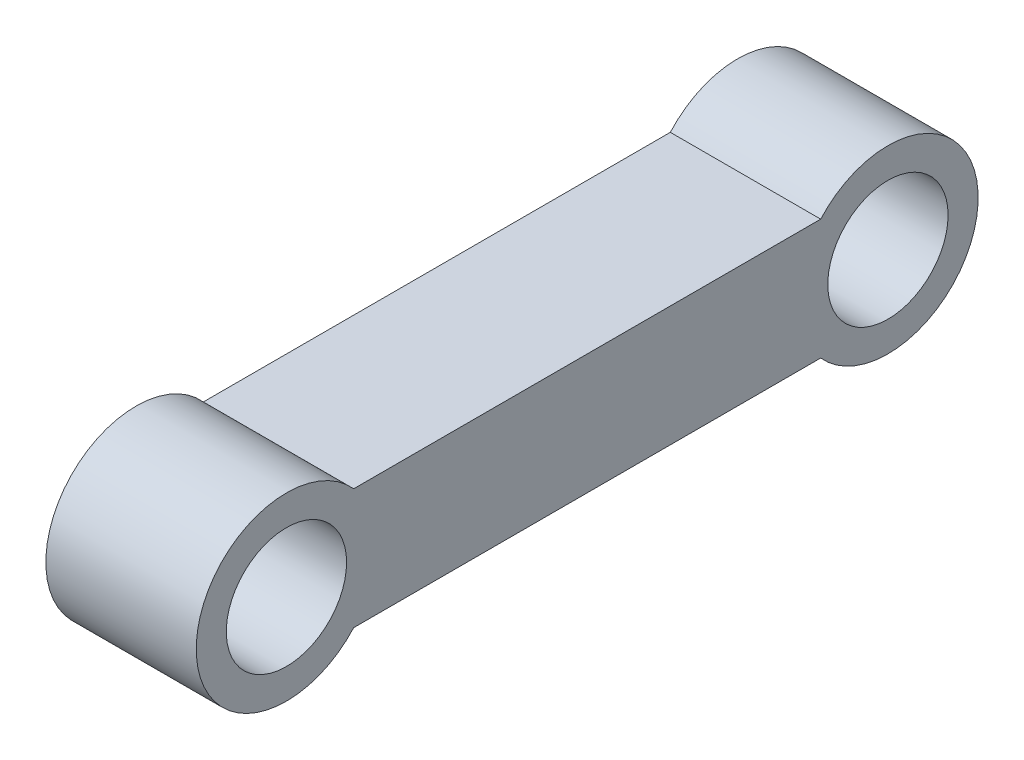
SolidWorks part; units mm, degrees
material "Thornel Mat VMA"
ref_plane "Front Plane" through (0, 0, 0) normal (0, 0, 1) x (1, 0, 0)
ref_plane "Top Plane" through (0, 0, 0) normal (0, 1, 0) x (1, 0, 0)
ref_plane "Right Plane" through (0, 0, 0) normal (1, 0, 0) x (0, 0, -1)
sketch "LinkFrame" plane through (0, 0, 0) normal (1, 0, 0) x (0, 0, -1)
  line L0 (-140.3455, -226.2633) -> (259.6545, -226.2633) construction
  line L1 (-95.6242, -186.2633) -> (214.9331, -186.2633)
  line L2 (-95.6242, -266.2633) -> (214.9331, -266.2633)
  arc A1 (214.9331, -266.2633) -> (214.9331, -186.2633) centre (259.6545, -226.2633) ccw
  arc A2 (-95.6242, -186.2633) -> (-95.6242, -266.2633) centre (-140.3455, -226.2633) ccw
  circle A5 centre (-140.3455, -226.2633) radius 40
  circle A6 centre (259.6545, -226.2633) radius 40
  dimension "D1" = 120
  dimension "D2" = 120
  dimension "D5" = 80
  dimension "D6" = 80
  dimension "D3" = 400
  dimension "D4" = 80
  dimension "D7" = 44.7214
  dimension "D8" = 44.7214
extrude "Boss-Extrude1" add sketch "LinkFrame" along normal blind 100
equation "\"D1@LinkFrame\" = 1.5 * \"HoleMountDiameter@PrintingPress.Assembly\""
equation "\"D2@LinkFrame\" = 1.5 * \"HoleMountDiameter@PrintingPress.Assembly\""
equation "\"LinkLength\"= 40cm"
equation "\"D3@LinkFrame\" = \"LinkLength\""
equation "\"D4@LinkFrame\" = \"HoleMountDiameter@PrintingPress.Assembly\""
equation "\"D5@LinkFrame\"=\"HoleMountDiameter@PrintingPress.Assembly\""
equation "\"D6@LinkFrame\"=\"HoleMountDiameter@PrintingPress.Assembly\""
equation "\"D1@Boss-Extrude1\"=\"RivetLength@PrintingPress.Assembly\""
